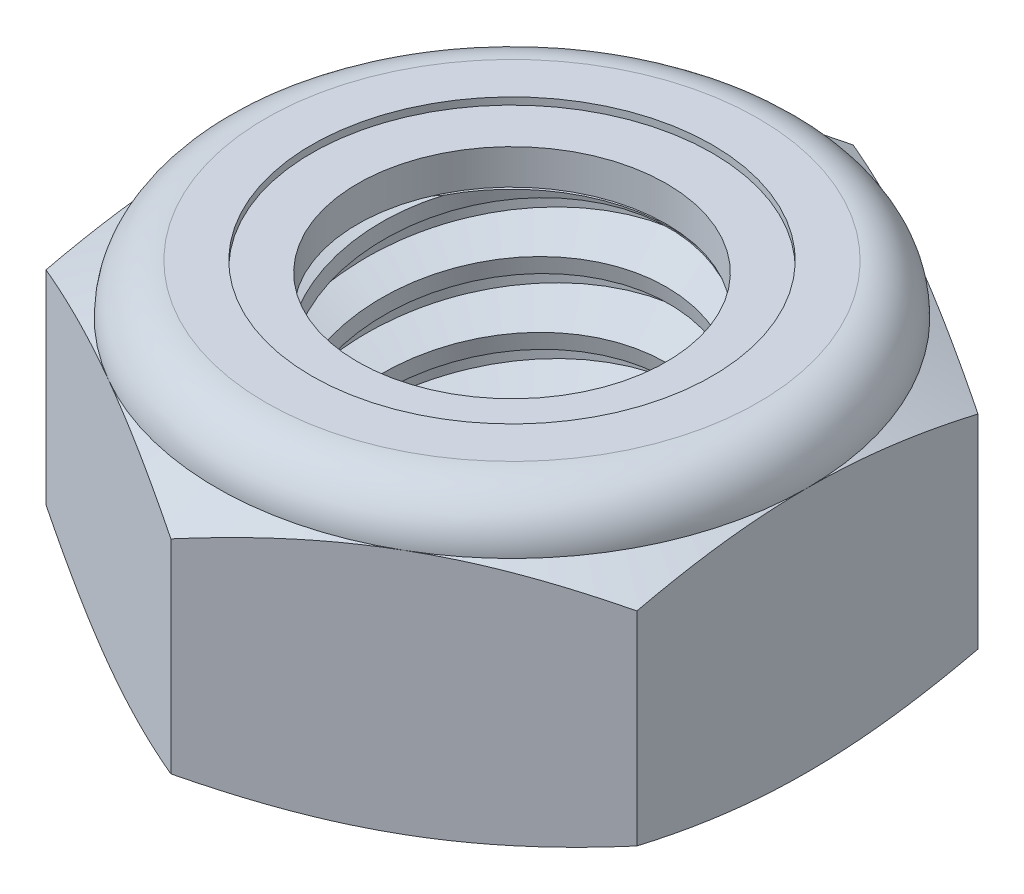
SolidWorks part; units mm, degrees
material "AISI 316 Annealed Stainless Steel Bar (SS)"
ref_plane "Front" through (0, 0, 0) normal (0, 0, 1) x (1, 0, 0)
ref_plane "Top" through (0, 0, 0) normal (0, 1, 0) x (1, 0, 0)
ref_plane "Right" through (0, 0, 0) normal (1, 0, 0) x (0, 0, -1)
sketch "Sketch1" plane through (0, 0, 0) normal (0, 1, 0) x (1, 0, 0)
  line L1 (0, 7.3323) -> (-6.35, 3.6662)
  line L2 (-6.35, 3.6662) -> (-6.35, -3.6662)
  line L3 (-6.35, -3.6662) -> (0, -7.3323)
  line L4 (0, -7.3323) -> (6.35, -3.6662)
  line L5 (6.35, -3.6662) -> (6.35, 3.6662)
  line L6 (6.35, 3.6662) -> (0, 7.3323)
  circle A0 centre (0, 0) radius 6.35 construction
  dimension "Hex Flats" = 12.7
extrude "Extrude1" add sketch "Sketch1" along normal blind 6.35
sketch "Sketch2" plane through (0, 0, 0) normal (1, 0, 0) x (0, 0, -1)
  line L0 (-3.9624, 0) -> (-3.9624, 6.35) construction
  line L1 (0, 0) -> (3.9624, 0)
  line L2 (0, 0) -> (0, 6.35)
  line L3 (0, 6.35) -> (3.9624, 6.35)
  line L4 (3.9624, 0) -> (3.9624, 6.35)
  line L5 (-3.6662, 6.35) -> (3.6662, 6.35) construction
  line L7 (0, -3.9624) -> (0, 0) construction
  dimension "Thread Dia" = 7.9248
revolve "Revolve1" add sketch "Sketch2" angle 360 about L7
sketch "Sketch3" plane through (0, 0, 0) normal (1, 0, 0) x (0, 0, -1)
  line L0 (3.9624, 6.35) -> (-3.9624, 6.35) construction
  line L1 (-3.9624, 6.35) -> (-3.9624, 4.9389) construction
  line L2 (-3.9624, 4.9389) -> (3.9624, 6.35) construction
  line L3 (3.9624, 6.35) -> (3.9933, 6.1763) construction
  line L4 (3.9933, 6.1763) -> (4.2098, 4.9607)
  line L5 (4.2098, 4.9607) -> (3.3805, 5.261)
  line L6 (3.3805, 5.261) -> (3.3187, 5.6083)
  line L7 (3.3187, 5.6083) -> (3.9933, 6.1763)
  line L8 (3.3496, 5.4346) -> (4.1015, 5.5685) construction
  line L9 (3.9624, 6.35) -> (3.9624, 5.5438) construction
  line L10 (3.9624, 5.5438) -> (-3.9624, 4.1327) construction
  line L11 (-3.9624, 4.1327) -> (-3.9624, 4.9389) construction
  line L12 (-0.2692, 6.35) -> (0.2692, 3.3264) construction
  line L13 (-3.9624, 0) -> (-3.9624, 6.35) construction
  line L14 (0, 6.35) -> (3.9624, 6.35) construction
  line L15 (3.9624, 0) -> (3.9624, 6.35) construction
  point P13 (0, 4.8382)
  dimension "D1" = 0.1764
  dimension "D2" = 0.3528
  dimension "Thread Pitch" = 1.4111
  dimension "D4" = 60
  dimension "D5" = 1.4111
revolve "Cut-Revolve1" cut sketch "Sketch3" angle 360 about L12
pattern_linear "LPattern1" count 5 spacing 1.4111 along (0, -1, 0) count 2 spacing 1.4111 along (0, 1, 0) of "Cut-Revolve1"
sketch "Sketch4" plane through (0, 0, 0) normal (1, 0, 0) x (0, 0, -1)
  line L0 (0, 6.35) -> (3.9624, 6.35)
  line L1 (3.9624, 6.35) -> (3.3187, 6.0498)
  line L2 (3.3187, 6.0498) -> (3.3187, 0.3002)
  line L3 (3.3187, 0.3002) -> (3.9624, 0)
  line L4 (3.9624, 0) -> (0, 0)
  line L5 (0, 0) -> (0, 6.35)
  line L6 (3.9624, 0) -> (3.9624, 6.35) construction
  line L7 (0, 6.35) -> (3.9624, 6.35) construction
  line L8 (0, 0) -> (3.9624, 0) construction
  line L9 (0, 0) -> (0, 6.35) construction
  line L10 (0, 6.35) -> (0, 7.0603) construction
  dimension "D1" = 25
revolve "Cut-Revolve2" cut sketch "Sketch4" angle 360 about L10
combine bodies "Combine1" operation type subtract main body 112 bodies to subtract 111
sketch "Sketch5" plane through (0, 0, 0) normal (1, 0, 0) x (0, 0, -1)
  line L0 (0, 0) -> (6.35, 0)
  line L1 (6.35, 0) -> (7.3323, 0.4581)
  line L2 (7.3323, 0.4581) -> (7.3323, 4.8336)
  line L3 (7.3323, 4.8336) -> (6.35, 5.2917)
  line L4 (5.2917, 6.35) -> (5.2917, 7.62)
  line L5 (5.2917, 7.62) -> (8.6023, 7.62)
  line L6 (8.6023, 7.62) -> (8.6023, -1.27)
  line L7 (8.6023, -1.27) -> (0, -1.27)
  line L8 (0, -1.27) -> (0, 0)
  line L9 (6.35, 5.2917) -> (6.35, 0) construction
  line L10 (0, 0) -> (3.9624, 0) construction
  line L13 (7.3323, 2.6458) -> (8.6023, 2.6458) construction
  line L14 (7.3323, 6.35) -> (7.3323, 0) construction
  line L15 (0, 0) -> (0, 7.62) construction
  line L20 (0, 7.62) -> (5.2917, 7.62) construction
  line L22 (0, 6.35) -> (3.9624, 6.35) construction
  arc A0 (6.35, 5.2917) -> (5.2917, 6.35) centre (5.2917, 5.2917) ccw
  dimension "D1" = 25
  dimension "D2" = 1.27
  dimension "D3" = 6.35
  dimension "D4" = 1.0583
revolve "Cut-Revolve3" cut sketch "Sketch5" angle 360 about L15
sketch "Sketch6" plane through (0, 0, 0) normal (1, 0, 0) x (0, 0, -1)
  line L0 (0, 5.2917) -> (6.1976, 5.2917)
  line L1 (5.2917, 6.1976) -> (4.3052, 6.1976)
  line L2 (0, 7.62) -> (0, 5.2917)
  line L3 (4.3052, 7.62) -> (0, 7.62)
  line L4 (0, 7.62) -> (5.2917, 7.62) construction
  line L5 (0, 0) -> (0, 7.62) construction
  line L6 (0, 7.62) -> (0, 44.323) construction
  line L7 (4.3052, 6.1976) -> (4.3052, 7.62)
  line L8 (5.2917, 6.35) -> (5.2917, 6.1976) construction
  line L9 (4.3052, 6.1976) -> (3.3187, 6.1976) construction
  line L10 (3.3187, 6.1976) -> (3.3187, 6.0498) construction
  arc A0 (6.1976, 5.2917) -> (5.2917, 6.1976) centre (5.2917, 5.2917) ccw
  arc A1 (6.35, 5.2917) -> (5.2917, 6.35) centre (5.2917, 5.2917) ccw construction
  dimension "D1" = 0.1524
revolve "Cut-Revolve4" cut sketch "Sketch6" angle 360 about L6
sketch "Sketch7" plane through (0, 0, 0) normal (1, 0, 0) x (0, 0, -1)
  line L0 (3.3187, 5.3679) -> (6.1179, 5.3679)
  line L1 (5.2917, 6.1214) -> (3.3187, 6.1214)
  line L2 (3.3187, 6.1214) -> (3.3187, 5.3679)
  line L3 (3.3187, 5.3679) -> (0, 5.3679) construction
  line L4 (0, 5.3679) -> (0, 6.1214) construction
  line L5 (0, 6.1214) -> (3.3187, 6.1214) construction
  line L6 (3.3187, 5.3679) -> (3.3187, 5.2917) construction
  line L7 (0, 5.2917) -> (6.1976, 5.2917) construction
  line L8 (5.2917, 6.1214) -> (5.2917, 6.1976) construction
  arc A0 (6.1179, 5.3679) -> (5.2917, 6.1214) centre (5.2917, 5.2917) ccw
  arc A2 (6.1976, 5.2917) -> (5.2917, 6.1976) centre (5.2917, 5.2917) ccw construction
  dimension "D1" = 0.0762
revolve "Revolve2" add sketch "Sketch7" angle 360 about L4
sketch "Sketch8" plane through (0, 0, 0) normal (0, -1, 0) x (1, 0, 0)
  arc A0 (3.9306, 0.5012) -> (-3.9306, 0.5012) centre (0, 0) ccw construction
  arc A1 (3.9306, 0.5012) -> (-3.9306, 0.5012) centre (0, 0) ccw
equation "\"D1@Sketch3\"=\"Thread Pitch@Sketch3\"/8"
equation "\"D2@Sketch3\"=\"Thread Pitch@Sketch3\"/4"
equation "\"D5@Sketch3\"=\"Thread Pitch@Sketch3\""
equation "\"D4@LPattern1\"=\"Thread Pitch@Sketch3\""
equation "\"D3@LPattern1\"=\"Thread Pitch@Sketch3\""
equation "\"D1@LPattern1\"=\"Height@Extrude1\"/\"Thread Pitch@Sketch3\""
equation "\"D4@Sketch5\"=\"Height@Extrude1\"/6"
